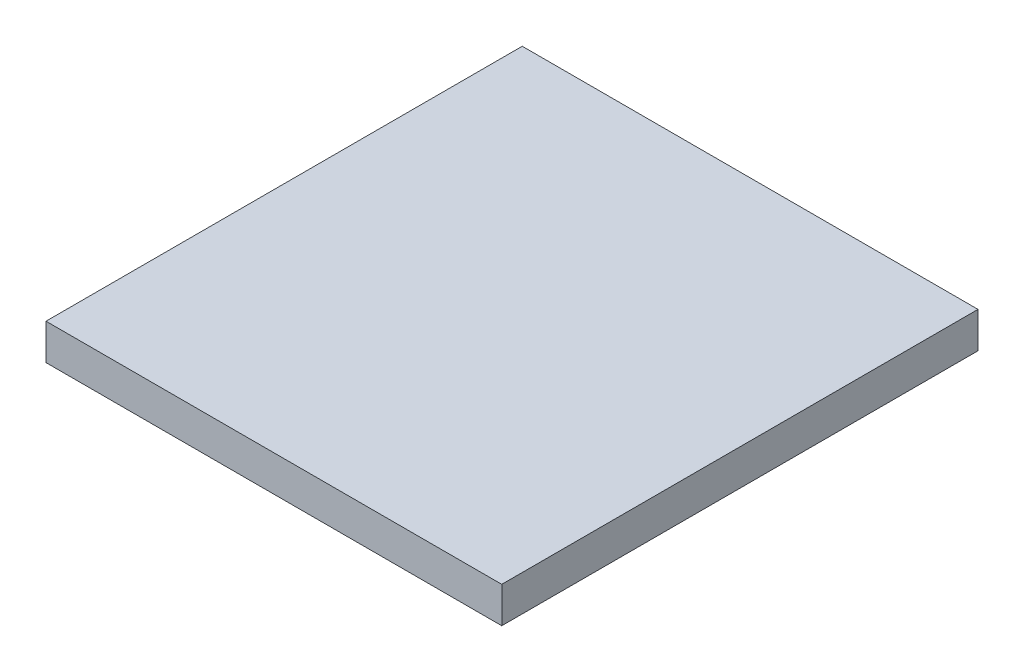
SolidWorks part; units mm, degrees
ref_plane "Front" through (0, 0, 0) normal (0, 0, 1) x (1, 0, 0)
ref_plane "Top" through (0, 0, 0) normal (0, 1, 0) x (1, 0, 0)
ref_plane "Right" through (0, 0, 0) normal (1, 0, 0) x (0, 0, -1)
sketch "Эскиз1" plane through (0, 0, 0) normal (0, 1, 0) x (1, 0, 0)
  line L1 (-10.16, 10.617) -> (10.16, 10.617)
  line L2 (-10.16, 10.617) -> (-10.16, -10.617)
  line L3 (-10.16, -10.617) -> (10.16, -10.617)
  line L4 (10.16, 10.617) -> (10.16, -10.617)
  line L5 (-10.16, 10.617) -> (10.16, -10.617) construction
  line L6 (-10.16, -10.617) -> (10.16, 10.617) construction
  point P0 (0, 0)
  dimension "D1" = 20.32
  dimension "D2" = 21.234
extrude "Бобышка-Вытянуть1" add sketch "Эскиз1" along normal blind 1.6
